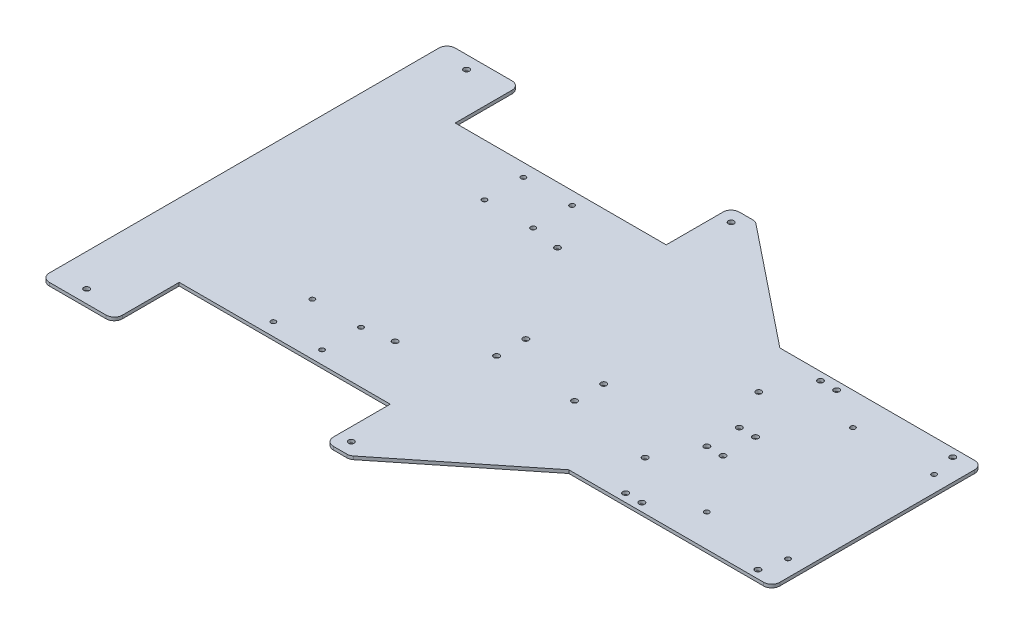
SolidWorks part; units mm, degrees
ref_plane "정면" through (0, 0, 0) normal (0, 0, 1) x (1, 0, 0)
ref_plane "윗면" through (0, 0, 0) normal (0, 1, 0) x (1, 0, 0)
ref_plane "우측면" through (0, 0, 0) normal (1, 0, 0) x (0, 0, -1)
sketch "스케치1" plane through (0, 0, 0) normal (0, 1, 0) x (1, 0, 0)
  line L1 (-195, -125) -> (195, -125)
  line L2 (-195, -125) -> (-195, 125)
  line L3 (-195, 125) -> (195, 125)
  line L4 (195, -125) -> (195, 125)
  line L5 (-195, -125) -> (195, 125) construction
  line L6 (-195, 125) -> (195, -125) construction
  point P0 (0, 0)
  dimension "D1" = 390
  dimension "D2" = 250
extrude "보스-돌출1" add sketch "스케치1" along normal blind 2
sketch "스케치2" plane through (0, 2, 0) normal (0, 1, 0) x (1, 0, 0)
  line L5 (195, 125) -> (-195, 125) construction
  line L6 (-150, 125) -> (-20, 125)
  line L7 (-150, 125) -> (-150, 85)
  line L8 (-150, 85) -> (-20, 85)
  line L9 (-20, 125) -> (-20, 85)
  line L10 (-150, -125) -> (-20, -125)
  line L11 (-150, -125) -> (-150, -85)
  line L12 (-150, -85) -> (-20, -85)
  line L13 (-20, -125) -> (-20, -85)
  line L14 (-195, -125) -> (195, -125) construction
  line L15 (70, 125) -> (195, 125)
  line L16 (70, 125) -> (70, 65)
  line L17 (70, 65) -> (195, 65)
  line L18 (195, 125) -> (195, 65)
  line L19 (70, -125) -> (195, -125)
  line L20 (70, -125) -> (70, -65)
  line L21 (70, -65) -> (195, -65)
  line L22 (195, -125) -> (195, -65)
  line L23 (195, -125) -> (195, 125) construction
  line L24 (-195, 125) -> (-195, -125) construction
  dimension "D1" = 130
  dimension "D2" = 40
  dimension "D3" = 40
  dimension "D4" = 60
  dimension "D5" = 60
  dimension "D6" = 45
  dimension "D7" = 125
extrude "컷-돌출1" cut sketch "스케치2" against normal blind 5
sketch "스케치3" plane through (0, 2, 0) normal (0, 1, 0) x (1, 0, 0)
  line L0 (-5, 125) -> (70, 65)
  line L2 (70, -65) -> (-5, -125)
  line L4 (-5, 125) -> (70, 125)
  line L5 (-5, -125) -> (70, -125)
  line L6 (70, -65) -> (70, -125)
  line L7 (70, 65) -> (70, 125)
  dimension "D1" = 75
  dimension "D2" = 75
extrude "컷-돌출2" cut sketch "스케치3" against normal blind 10
fillet "필렛1" radius 5 10 edges at (-20, 1, 125) (-20, 1, -125) (-5, 1, 125) (-5, 1, -125) (195, 1, -65) (195, 1, 65) (-195, 1, -125) (-195, 1, 125) (-150, 1, -125) (-150, 1, 125)
sketch "스케치4" plane through (0, 2, 0) normal (0, 1, 0) x (1, 0, 0)
  line L0 (-195, 0) -> (195, 0) construction
  line L1 (-100, 77) -> (-70, 77) construction
  line L2 (-100, 77) -> (-100, 53) construction
  line L3 (-100, 53) -> (-70, 53) construction
  line L4 (-70, 77) -> (-70, 53) construction
  line L5 (-100, 77) -> (-70, 53) construction
  line L6 (-100, 53) -> (-70, 77) construction
  line L7 (-195, 120) -> (-195, -120) construction
  line L8 (195, -60) -> (195, 60) construction
  line L9 (-150, 85) -> (-20, 85) construction
  line L10 (-100, -53) -> (-70, -77) construction
  line L11 (-100, -77) -> (-70, -53) construction
  line L12 (-70, -77) -> (-70, -53) construction
  line L13 (-100, -53) -> (-70, -53) construction
  line L14 (-100, -77) -> (-100, -53) construction
  line L15 (-100, -77) -> (-70, -77) construction
  line L17 (100, -60) -> (110, -60) construction
  line L18 (100, -60) -> (100, 60) construction
  line L19 (100, 60) -> (110, 60) construction
  line L20 (110, -60) -> (110, 60) construction
  line L21 (100, -60) -> (110, 60) construction
  line L22 (100, 60) -> (110, -60) construction
  line L23 (100, -10) -> (110, -10) construction
  line L24 (100, -10) -> (100, 10) construction
  line L25 (100, 10) -> (110, 10) construction
  line L26 (110, -10) -> (110, 10) construction
  line L27 (100, -10) -> (110, 10) construction
  line L28 (100, 10) -> (110, -10) construction
  circle A0 centre (-100, 77) radius 1.5
  circle A1 centre (-70, 77) radius 1.5
  circle A2 centre (-70, 53) radius 1.5
  circle A3 centre (-100, 53) radius 1.5
  circle A4 centre (-100, -53) radius 1.5
  circle A5 centre (-70, -53) radius 1.5
  circle A6 centre (-70, -77) radius 1.5
  circle A7 centre (-100, -77) radius 1.5
  circle A8 centre (100, 60) radius 1.75
  circle A9 centre (110, 60) radius 1.75
  circle A10 centre (100, 10) radius 1.75
  circle A11 centre (110, 10) radius 1.75
  circle A12 centre (100, -10) radius 1.75
  circle A13 centre (110, -10) radius 1.75
  circle A14 centre (100, -60) radius 1.75
  circle A15 centre (110, -60) radius 1.75
  point P0 (-85, 65)
  point P25 (-85, -65)
  point P26 (105, 0)
  point P31 (105, 0)
  dimension "D5" = 3
  dimension "D9" = 3.5
  dimension "D1" = 30
  dimension "D2" = 24
  dimension "D3" = 95
  dimension "D4" = 32
  dimension "D6" = 120
  dimension "D7" = 10
  dimension "D8" = 20
  dimension "D10" = 85
extrude "컷-돌출3" cut sketch "스케치4" against normal through all
sketch "스케치5" plane through (0, 2, 0) normal (0, 1, 0) x (1, 0, 0)
  line L0 (-20, -85) -> (-150, -85) construction
  line L1 (-13, -26.5) -> (35, -26.5) construction
  line L2 (-13, -26.5) -> (-13, -8.5) construction
  line L3 (-13, -8.5) -> (35, -8.5) construction
  line L4 (35, -26.5) -> (35, -8.5) construction
  line L5 (195, -60) -> (195, 60) construction
  circle A1 centre (-13, -8.5) radius 1.75
  circle A2 centre (35, -8.5) radius 1.75
  circle A3 centre (-13, -26.5) radius 1.75
  circle A4 centre (35, -26.5) radius 1.75
  dimension "D1" = 3.5
  dimension "D2" = 58.5
  dimension "D3" = 18
  dimension "D4" = 48
  dimension "D5" = 160
extrude "컷-돌출4" cut sketch "스케치5" against normal through all
sketch "스케치6" plane through (0, 2, 0) normal (0, 1, 0) x (1, 0, 0)
  line L0 (70, 65) -> (190, 65) construction
  line L1 (135, 45) -> (185, 45) construction
  line L2 (135, 45) -> (135, -45) construction
  line L3 (135, -45) -> (185, -45) construction
  line L4 (185, 45) -> (185, -45) construction
  line L5 (190, -65) -> (70, -65) construction
  line L6 (195, -60) -> (195, 60) construction
  circle A0 centre (135, 45) radius 1.5
  circle A1 centre (185, 45) radius 1.5
  circle A2 centre (135, -45) radius 1.5
  circle A3 centre (185, -45) radius 1.5
  dimension "D5" = 3
  dimension "D1" = 20
  dimension "D2" = 20
  dimension "D3" = 10
  dimension "D4" = 50
extrude "컷-돌출5" cut sketch "스케치6" against normal through all
sketch "스케치7" plane through (0, 2, 0) normal (0, 1, 0) x (1, 0, 0)
  line L0 (-6.7539, 125) -> (-15, 125) construction
  line L1 (-175, 117) -> (-12, 117) construction
  line L2 (-175, 117) -> (-175, -117) construction
  line L3 (-175, -117) -> (-12, -117) construction
  line L4 (-12, 117) -> (-12, -117) construction
  line L5 (-20, 85) -> (-20, 120) construction
  line L6 (-15, -125) -> (-6.7539, -125) construction
  line L7 (-52, 50) -> (-52, -50) construction
  line L8 (-195, 120) -> (-195, -120) construction
  line L9 (181.5, 60) -> (181.5, -60) construction
  line L10 (195, -60) -> (195, 60) construction
  line L11 (190, -65) -> (70, -65) construction
  line L12 (70, 65) -> (190, 65) construction
  line L13 (87, 35) -> (87, -35) construction
  line L14 (-150, 85) -> (-20, 85) construction
  line L15 (-20, -85) -> (-150, -85) construction
  circle A0 centre (-12, 117) radius 1.75
  circle A1 centre (-12, -117) radius 1.75
  circle A2 centre (181.5, 60) radius 1.75
  circle A3 centre (181.5, -60) radius 1.75
  circle A4 centre (-175, 117) radius 1.75
  circle A5 centre (-175, -117) radius 1.75
  circle A6 centre (87, 35) radius 1.75
  circle A7 centre (87, -35) radius 1.75
  circle A9 centre (-52, 50) radius 1.75
  circle A10 centre (-52, -50) radius 1.75
  dimension "D1" = 8
  dimension "D2" = 8
  dimension "D3" = 8
  dimension "D4" = 20
  dimension "D5" = 3.5
  dimension "D7" = 5
  dimension "D8" = 5
  dimension "D10" = 30
  dimension "D11" = 108
  dimension "D13" = 35
  dimension "D14" = 35
  dimension "D6" = 13.5
  dimension "D9" = 70
  dimension "D12" = 40
extrude "컷-돌출6" cut sketch "스케치7" against normal through all
